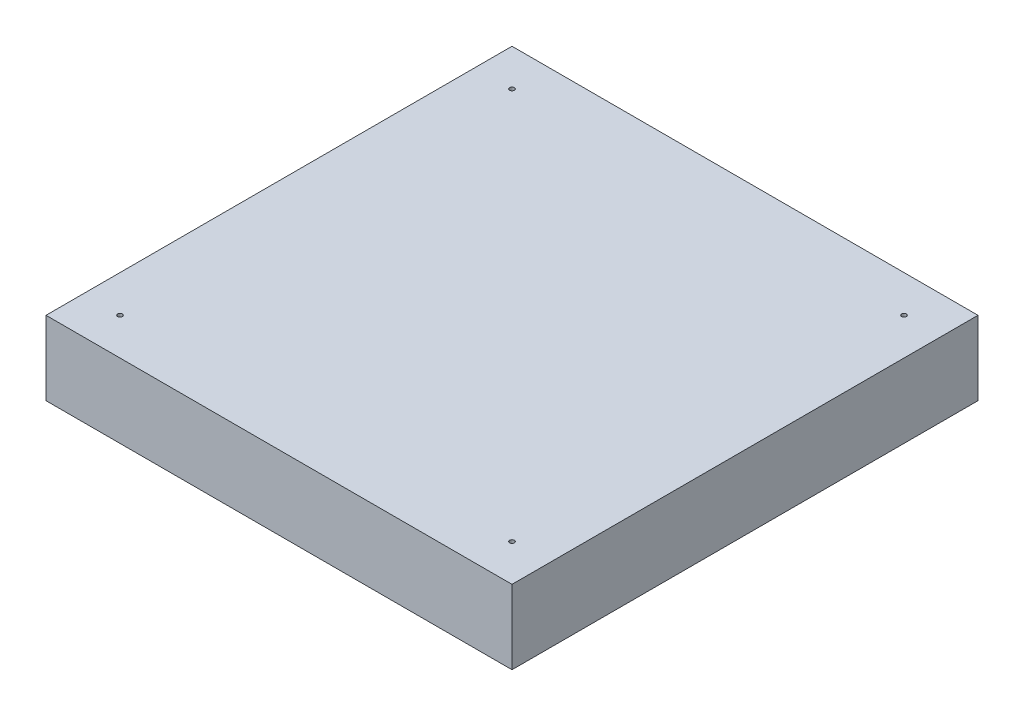
SolidWorks part; units mm, degrees
note: '?' marks a value the reader was unsure of.
material "Balsa"
ref_plane "Front Plane" through (0, 0, 0) normal (0, 0, 1) x (1, 0, 0)
ref_plane "Top Plane" through (0, 0, 0) normal (0, 1, 0) x (1, 0, 0)
ref_plane "Right Plane" through (0, 0, 0) normal (1, 0, 0) x (0, 0, -1)
sketch "Sketch1" plane through (0, 0, 0) normal (0, 1, 0) x (1, 0, 0)
  line L5 (-80, -80) -> (80, -80)
  line L6 (-80, -80) -> (-80, 80)
  line L7 (-80, 80) -> (80, 80)
  line L8 (80, -80) -> (80, 80)
  line L9 (-80, -80) -> (80, 80) construction
  line L10 (-80, 80) -> (80, -80) construction
  point P0 (0, 0)
  dimension "D1" = 160
  dimension "D2" = 160
extrude "Boss-Extrude1" add sketch "Sketch1" along normal blind 25.4
hole_wizard "CBORE for #0 Binding Head Machine Screw1" positions "Sketch2" profile "Sketch3" counterbore size "#0" standard "ANSI Inch" end condition through all
sketch "Sketch2" plane through (0, 0, 0) normal (0, 1, 0) x (1, 0, 0)
  line L0 (-80, -80) -> (80, -80) construction
  line L1 (-80, 80) -> (-80, -80) construction
  line L2 (0, 0) -> (112.6922, 0) construction
  line L5 (0, 0) -> (0, 110.9847) construction
  point P0 (-67.3, 67.3)
  point P2 (67.3, 67.3)
  point P4 (67.3, -67.3)
  point P6 (-67.3, -67.3)
  dimension "D1" = 12.7
  dimension "D2" = 12.7
sketch "Sketch3" plane through (-67.3, 0, -67.3) normal (1, 0, 0) x (0, 0, -1)
  line L0 (0, 0) -> (0, 25.4)
  line L1 (0, 25.4) -> (0.8065, 25.4)
  line L3 (0.8065, 25.4) -> (0.8065, 0.8128)
  line L4 (1.985, 0.8128) -> (0.8065, 0.8128)
  line L5 (1.985, 0.8128) -> (1.985, 0.8725)
  line L6 (1.985, 0.8725) -> (2.8575, 0)
  line L7 (2.8575, 0) -> (0, 0)
  line L8 (-1.985, 0.8725) -> (-2.8575, 0) construction
  line L11 (0, -6.35) -> (0, 107.95) construction
  dimension "Thru Hole Dia." = 1.6129
  dimension "Thru Hole Depth" = 25.4
  dimension "C'Bore Dia." = 3.97
  dimension "C'Bore Depth" = 0.8128
  dimension "Near C'Sink Dia." = 5.715
  dimension "Near C'Sink Angle" = 90
ref_axis "Axis1" through (0, 26.67, 0) along (0, -1, 0)?
hole_wizard "CBORE for #0 Binding Head Machine Screw2" [suppressed] positions "Sketch4" profile "Sketch5" counterbore size "#0" standard "ANSI Inch"
sketch "Sketch4" plane through (0, 25.4, 0) normal (0, 1, 0) x (1, 0, 0)
  line L1 (-80, 80) -> (-80, -80) construction
  circle A0 centre (-67.3, 67.3) radius 0.8065 construction
  circle A1 centre (-67.3, -67.3) radius 0.8065 construction
  point P0 (-67.3005, 29.2)
  point P2 (-67.3005, -29.2)
  dimension "D1" = 38.1
  dimension "D2" = 38.1
  dimension "D3" = 12.6995
sketch "Sketch5" plane through (-67.3005, 25.4, -29.2) normal (1, 0, 0) x (0, 0, 1)
  line L0 (0, 0) -> (0, 25.4)
  line L1 (0, 25.4) -> (0.8065, 25.4)
  line L3 (0.8065, 25.4) -> (0.8065, 0.8128)
  line L4 (1.985, 0.8128) -> (0.8065, 0.8128)
  line L5 (1.985, 0.8128) -> (1.985, 0.8725)
  line L6 (1.985, 0.8725) -> (2.8575, 0)
  line L7 (2.8575, 0) -> (0, 0)
  line L8 (-1.985, 0.8725) -> (-2.8575, 0) construction
  line L11 (0, -6.35) -> (0, 107.95) construction
  dimension "Thru Hole Dia." = 1.6129
  dimension "Thru Hole Depth" = 25.4
  dimension "C'Bore Dia." = 3.97
  dimension "C'Bore Depth" = 0.8128
  dimension "Near C'Sink Dia." = 5.715
  dimension "Near C'Sink Angle" = 90
pattern_circular "CirPattern1" [suppressed] count 4 over 360 about axis through (0, 26.67, 0) along (0, -1, 0)
sketch "Sketch6" [suppressed] plane through (0, 25.4, 0) normal (0, 1, 0) x (1, 0, 0)
  circle A0 centre (0, 0) radius 25.4
extrude "Cut-Extrude1" [suppressed] cut sketch "Sketch6" against normal through all
